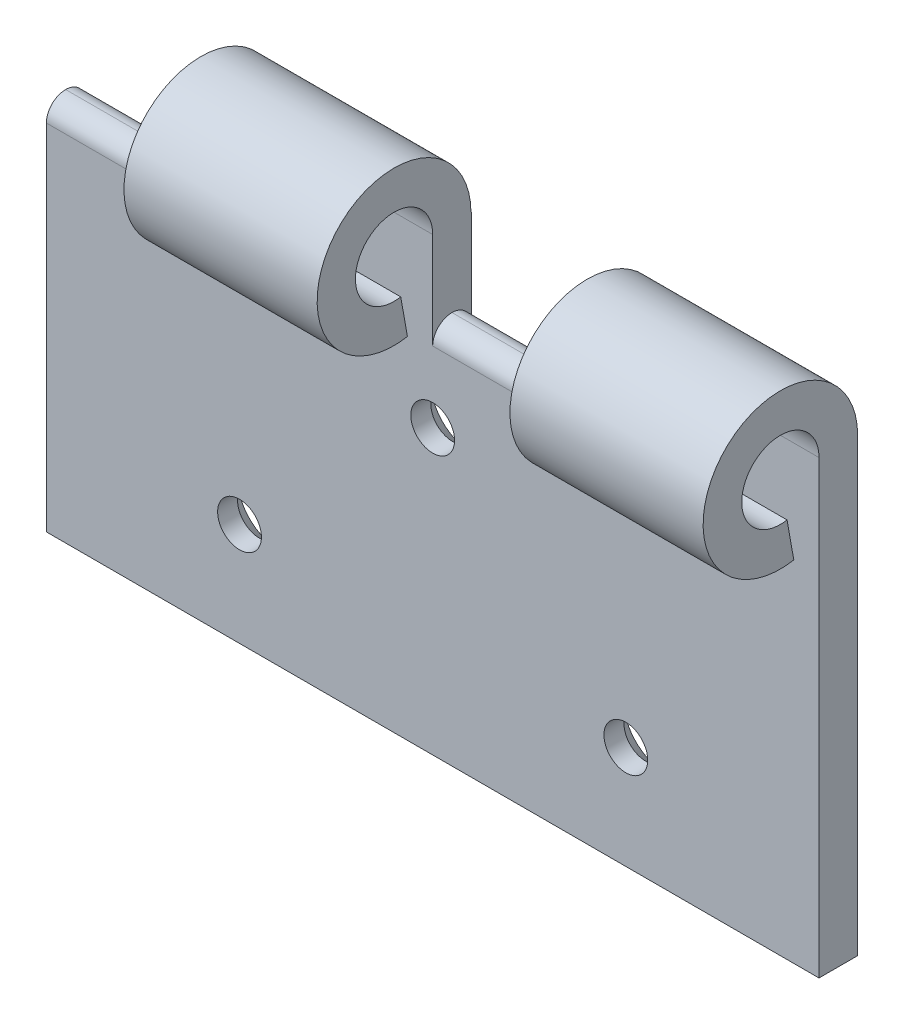
SolidWorks part; units mm, degrees
material "PET"
ref_plane "Front Plane" through (0, 0, 0) normal (0, 0, 1) x (1, 0, 0)
ref_plane "Top Plane" through (0, 0, 0) normal (0, 1, 0) x (1, 0, 0)
ref_plane "Right Plane" through (0, 0, 0) normal (1, 0, 0) x (0, 0, -1)
sketch "Sketch1" plane through (0, 0, 0) normal (0, 0, 1) x (1, 0, 0)
  line L1 (-30, -17.5) -> (30, -17.5)
  line L2 (-30, -17.5) -> (-30, 17.5)
  line L3 (-30, 17.5) -> (30, 17.5)
  line L4 (30, -17.5) -> (30, 17.5)
  line L5 (-30, -17.5) -> (30, 17.5) construction
  line L6 (-30, 17.5) -> (30, -17.5) construction
  point P0 (0, 0)
  dimension "D2" = 35
  dimension "D3" = 60
extrude "Boss-Extrude1" add sketch "Sketch1" along normal blind 3 contours L1 L4 L3 L2 region at (0, 0, 0)
sketch "Sketch2" plane through (0, 0, 0) normal (0, 0, 1) x (1, 0, 0)
  point P0 (0, 4.5)
  point P2 (-15, -9.5)
  point P4 (15, -9.5)
  dimension "D1" = 4.5
  dimension "D2" = 9.5
  dimension "D3" = 9.5
  dimension "D4" = 15
  dimension "D5" = 15
hole_wizard "CSK for M3 Countersunk Flat Head Screw1" positions "Sketch2" profile "Sketch3" countersink size "M3" standard "ISO"
sketch "Sketch3" plane through (0, 4.5, 0) normal (1, 0, 0) x (0, 1, 0)
  line L0 (0, 0) -> (0, 4.0215)
  line L1 (0, 4.0215) -> (1.7, 3)
  line L2 (1.7, 3) -> (1.7, 1.45)
  line L3 (1.7, 1.45) -> (3.15, 0)
  line L5 (3.15, 0) -> (0, 0)
  line L6 (-1.7, 1.45) -> (-3.15, 0) construction
  line L10 (0, 4.0215) -> (-1.7, 3) construction
  line L11 (0, -6.35) -> (0, 107.95) construction
  dimension "Hole Dia." = 3.4
  dimension "Hole Depth" = 3
  dimension "Near C'Sink Dia." = 6.3
  dimension "Near C'Sink Angle" = 90
  dimension "Drill Angle" = 118
sketch "Sketch5" plane through (30, 0, 0) normal (1, 0, 0) x (0, 0, -1)
  line L0 (0, 17.5) -> (-6, 17.5) construction
  line L1 (0, -17.5) -> (0, 17.5) construction
  line L2 (-6, 17.5) -> (-5.4791, 14.5456) construction
  line L5 (-3, -17.5) -> (-3, 17.5) construction
  line L6 (-5.4791, 14.5456) -> (-4.9581, 11.5912)
  line L7 (-3, 17.5) -> (-3, 12.3038)
  arc A0 (-3, 12.3038) -> (-4.9581, 11.5912) centre (-6, 17.5) ccw
  arc A1 (-3, 17.5) -> (-5.4791, 14.5456) centre (-6, 17.5) ccw
  circle A2 centre (-6, 17.5) radius 3 construction
  circle A3 centre (-6, 17.5) radius 6 construction
  dimension "D1" = 6
  dimension "D3" = 80
  dimension "D2" = 3
extrude "Boss-Extrude2" add sketch "Sketch5" against normal blind 15
sketch "Sketch6" plane through (0, 0, 0) normal (-1, 0, 0) x (0, 0, 1)
  line L0 (3, 17.5) -> (3, 12.3353)
  line L1 (3, -17.5) -> (3, 17.5) construction
  line L3 (5.4791, 14.5456) -> (4.9581, 11.5912)
  arc A2 (4.9628, 11.6179) -> (3, 12.3353) centre (6, 17.5) ccw
  arc A3 (5.4791, 14.5456) -> (3, 17.5) centre (6, 17.5) ccw
  dimension "D1" = 11.9456
extrude "Boss-Extrude3" add sketch "Sketch6" along normal blind 15 contours L3 A3 L0 A2 | A2 L0 A3 L3 region at (0, 14.9176, 2.8311)
sketch "Sketch8" plane through (0, 0, 0) normal (1, 0, 0) x (0, 0, -1)
  line L6 (0, 17.5) -> (0, -17.5) construction
  line L7 (-3, 17.5) -> (0, 17.5)
  line L8 (-3, 17.5) -> (-3, 11.5)
  line L9 (-3, 11.5) -> (0, 11.5)
  line L10 (0, 17.5) -> (0, 11.5)
  dimension "D1" = 6
sketch "Sketch9" plane through (-15, 0, 0) normal (-1, 0, 0) x (0, 0, 1)
  line L3 (0, 17.5) -> (0.0048, 17.5)
  line L10 (0.0048, 17.5) -> (0, 17.5)
  line L15 (0, 17.5) -> (3, 17.5)
  line L16 (0, 17.5) -> (0, 11.5)
  line L17 (0, 11.5) -> (3, 11.5)
  line L18 (3, 17.5) -> (3, 11.5)
  line M3 (0.0272, 17.5) -> (3, 17.5)
extrude "Cut-Extrude4" cut sketch "Sketch9" along normal blind 15 contours L18 L15 L3 L16 L17 M3 region at (-15, 14.5, 1.5)
extrude "Cut-Extrude5" cut sketch "Sketch8" along normal blind 15
fillet "Fillet4" radius 1.5 4 edges at (-22.5, 11.5, 0) (-22.5, 11.5, 3) (7.5, 11.5, 0) (7.5, 11.5, 3)
